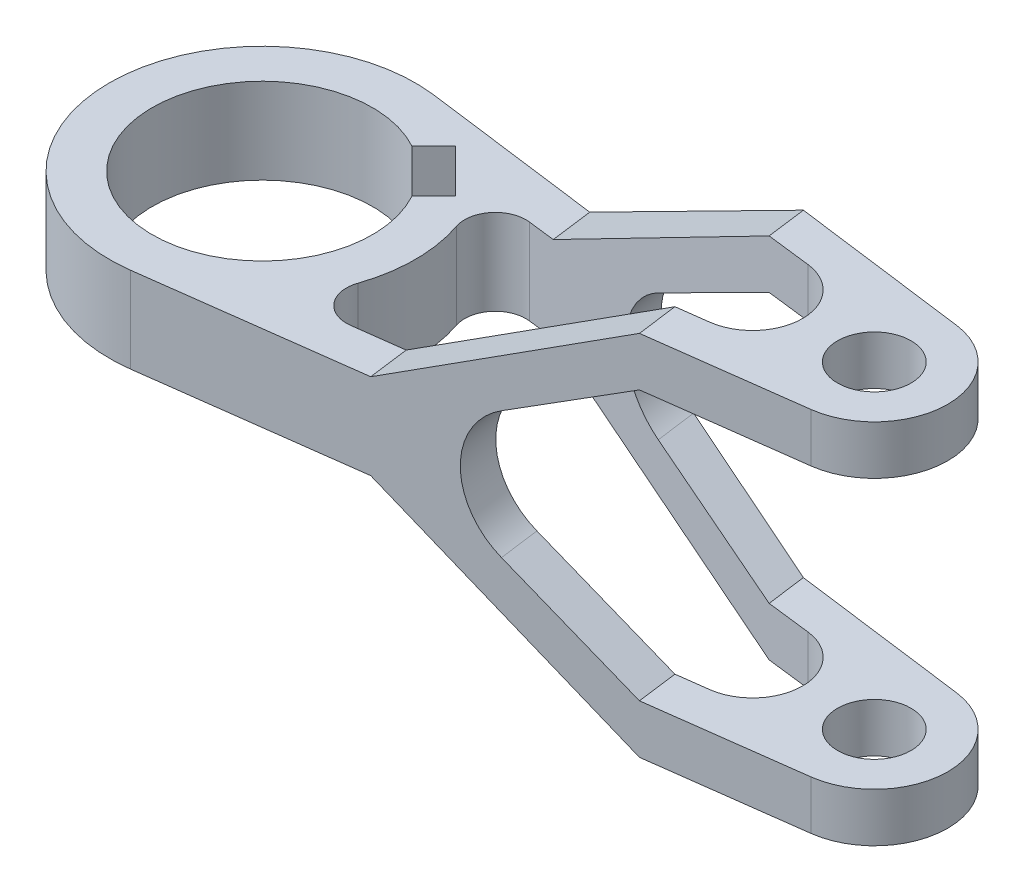
SolidWorks part; units mm, degrees
ref_plane "Front Plane" through (0, 0, 0) normal (0, 0, 1) x (1, 0, 0)
ref_plane "Top Plane" through (0, 0, 0) normal (0, 1, 0) x (1, 0, 0)
ref_plane "Right Plane" through (0, 0, 0) normal (1, 0, 0) x (0, 0, -1)
sketch "Sketch1" plane through (0, 0, 0) normal (0, 1, 0) x (1, 0, 0)
  line L0 (3.25, 24.7878) -> (101.56, 11.8982)
  line L1 (-55, 0) -> (55, 0) construction
  line L2 (3.25, -24.7878) -> (101.56, -11.8982)
  line L3 (29.0016, 14.6255) -> (80.8254, 8.3614)
  line L4 (29.0516, -14.6192) -> (80.907, -7.8203)
  arc A0 (3.25, 24.7878) -> (3.25, -24.7878) centre (0, 0) ccw
  circle A1 centre (0, 0) radius 18
  arc A2 (101.56, -11.8982) -> (101.56, 11.8982) centre (100, 0) ccw
  circle A3 centre (100, 0) radius 6
  arc A5 (80.907, -7.8203) -> (80.8254, 8.3614) centre (79.8468, 0.2654) ccw
  arc A6 (29.0016, 14.6255) -> (23.668, 8.0513) centre (28.4016, 9.6616) ccw
  arc A7 (29.0516, -14.6192) -> (23.668, -8.0513) centre (28.4016, -9.6616) cw
  arc A8 (23.668, -8.0513) -> (23.668, 8.0513) centre (0, 0) ccw
  dimension "D1" = 50
  dimension "D2" = 36
  dimension "D3" = 24
  dimension "D4" = 12
  dimension "D6" = 10
  dimension "D5" = 100
extrude "Boss-Extrude1" add sketch "Sketch1" along normal blind 30 and the other way blind 30
sketch "Sketch2" plane through (3.25, 0, 24.7878) normal (0.13, 0, 0.9915) x (0.9915, 0, -0.13)
  line L2 (-25, 30) -> (-25, -30) construction
  line L5 (-25, 30) -> (-25, 7)
  line L6 (-25, 7) -> (35, 7)
  line L7 (35, 7) -> (74.1514, 30)
  line L8 (-25, 30) -> (74.1514, 30)
  line L9 (111.1514, -30) -> (111.1514, 30) construction
  point P0 (54.2136, 30)
  dimension "D1" = 60
  dimension "D2" = 7
  dimension "D3" = 37
extrude "Cut-Extrude1" cut sketch "Sketch2" against normal through all
mirror "Mirror1" about plane through (0, 0, 0) normal (0, 1, 0) of "Cut-Extrude1"
sketch "Sketch3" plane through (3.25, 0, 24.7878) normal (0.13, 0, 0.9915) x (0.9915, 0, -0.13)
  line L0 (111.1514, -30) -> (111.1514, 30) construction
  line L1 (111.1514, -22) -> (111.1514, 22)
  line L2 (111.1514, 22) -> (74.1514, 22)
  line L5 (74.1514, -22) -> (111.1514, -22)
  line L6 (74.1514, 30) -> (99.1514, 30) construction
  line L7 (54.0463, 10.3923) -> (74.1514, 22)
  line L8 (54.0463, -10.3923) -> (74.1514, -22)
  line L9 (74.1514, -30) -> (99.1514, -30) construction
  arc A0 (54.0463, 10.3923) -> (54.0463, -10.3923) centre (60.0463, 0) ccw
  point P15 (60.8529, 0)
  dimension "D3" = 24
  dimension "D1" = 8
  dimension "D2" = 37
  dimension "D4" = 37
  dimension "D5" = 8
  dimension "D6" = 60
extrude "Cut-Extrude2" cut sketch "Sketch3" against normal through all
sketch "Sketch4" plane through (0, 7, 0) normal (0, 1, 0) x (1, 0, 0)
  line L0 (0, 0) -> (39.5051, 0) construction
  line L1 (0, 0) -> (35.6175, 35.6175) construction
  line L2 (8.6915, 15.7626) -> (12.227, 19.2981)
  line L3 (12.227, 19.2981) -> (19.2981, 12.227)
  line L4 (19.2981, 12.227) -> (15.7626, 8.6915)
  circle A0 centre (0, 0) radius 18 construction
  arc A1 (15.7626, 8.6915) -> (8.6915, 15.7626) centre (0, 0) ccw
  dimension "D1" = 45
  dimension "D2" = 10
  dimension "D3" = 5
extrude "Cut-Extrude3" cut sketch "Sketch4" against normal through all
